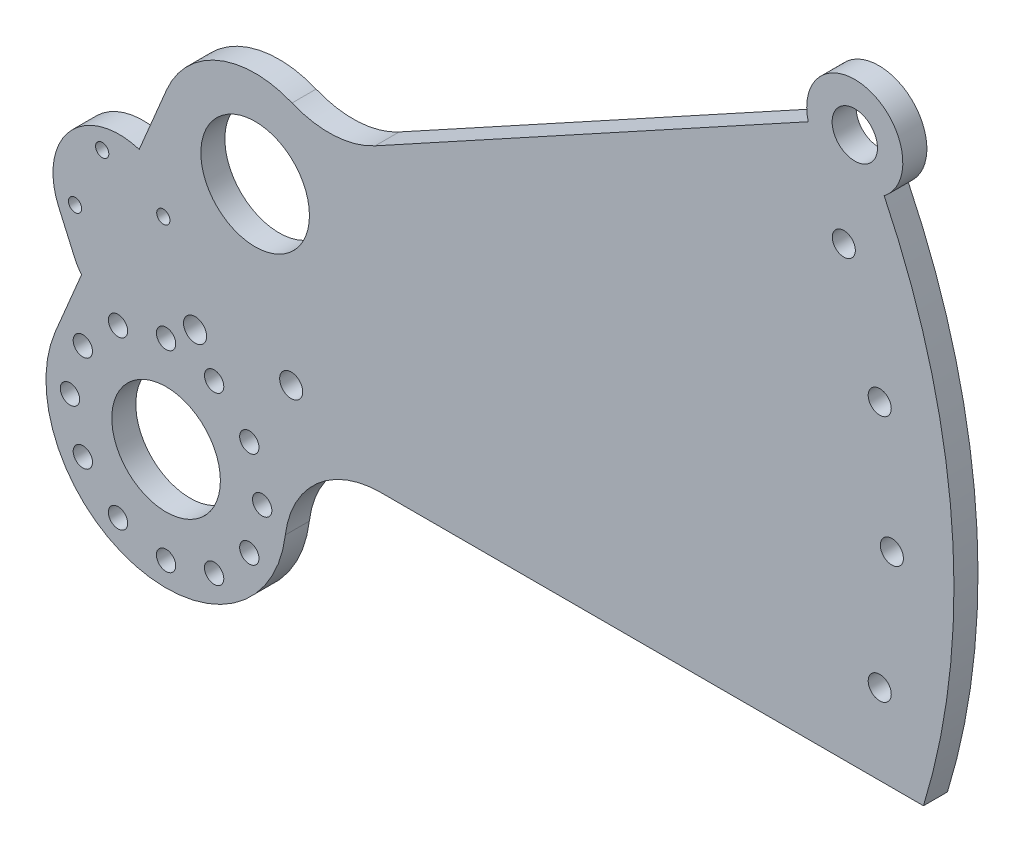
SolidWorks part; units mm, degrees
material "6061-T6 (SS)"
ref_plane "Front Plane" through (0, 0, 0) normal (0, 0, 1) x (1, 0, 0)
ref_plane "Top Plane" through (0, 0, 0) normal (0, 1, 0) x (1, 0, 0)
ref_plane "Right Plane" through (0, 0, 0) normal (1, 0, 0) x (0, 0, -1)
ref_plane "Plane1" through (0, 0, 0) normal (0, 0, -1) x (-1, 0, 0)
sketch "Sketch1" plane through (0, 0, 0) normal (0, 0, -1) x (-1, 0, 0)
  line L7 (-31.7217, 24.6299) -> (-146.1701, 87.3654)
  line L8 (-176.627, -53.975) -> (-33.1944, -53.975)
  line L9 (52.8124, -60.1841) -> (45.8592, -43.6206)
  line L10 (47.5699, -41.0132) -> (51.9346, -31.1397)
  line L11 (30.6457, -7.3807) -> (23.42, 9.8317)
  line L12 (0, 0) -> (35.9287, -24.0642) construction
  line L13 (35.9287, -24.0642) -> (47.5935, -28.5567) construction
  line L14 (35.9287, -24.0642) -> (40.4212, -12.3994) construction
  line L15 (35.9287, -24.0642) -> (24.2639, -19.5717) construction
  line L16 (35.9287, -24.0642) -> (46.3362, -24.0642) construction
  line L17 (23.5374, -72.4737) -> (0, 0) construction
  line L18 (48.9374, -72.4737) -> (23.5374, -72.4737) construction
  line L19 (23.5374, -72.4737) -> (48.9374, -72.4737) construction
  line L20 (15.875, -41.275) -> (0, 0) construction
  line L21 (-9.525, -41.275) -> (15.875, -41.275) construction
  line L22 (-207.782, -132.6531) -> (-57.7705, -132.6531) construction
  line L23 (-57.7705, -132.6531) -> (92.241, -132.6531) construction
  line L24 (0, 0) -> (-168.275, 0) construction
  line L25 (-165.0688, -32.6918) -> (0, 0) construction
  line L26 (0, 0) -> (-165.0688, 32.6918) construction
  line L27 (-155.5725, 64.1379) -> (0, 0) construction
  line L28 (-165.0688, -32.6918) -> (-168.275, 0) construction
  line L29 (-168.275, 0) -> (-165.0688, 32.6918) construction
  line L30 (-165.0688, 32.6918) -> (-155.5725, 64.1379) construction
  circle A0 centre (40.4212, -12.3994) radius 1.75
  circle A1 centre (47.5935, -28.5567) radius 1.75
  circle A2 centre (15.875, -41.275) radius 3.048
  circle A3 centre (45.5344, -85.1737) radius 2.5527
  circle A4 centre (48.9374, -72.4737) radius 2.5527
  circle A5 centre (23.5374, -72.4737) radius 14.351
  circle A6 centre (-9.525, -41.275) radius 3.048
  circle A11 centre (-165.0688, 32.6918) radius 3.048
  circle A12 centre (-165.0688, -32.6918) radius 3.048
  circle A22 centre (-155.5725, 64.1379) radius 3.048
  circle A23 centre (-168.275, 0) radius 3.048
  circle A24 centre (0, 0) radius 14.351
  circle A38 centre (24.2639, -19.5717) radius 1.75
  circle A39 centre (-158.4749, 90.5087) radius 5.9944
  arc A40 (-146.1701, 87.3654) -> (-166.2421, 80.4608) centre (-158.4749, 90.5087) ccw
  arc A41 (-166.2421, 80.4608) -> (-176.627, -53.975) centre (0, 0) ccw
  arc A42 (-33.1944, -53.975) -> (-7.9803, -76.3077) centre (-33.1944, -79.375) cw
  arc A43 (-7.9803, -76.3077) -> (52.8124, -60.1841) centre (23.5374, -72.4737) ccw
  arc A44 (45.8592, -43.6206) -> (47.5699, -41.0132) centre (38.8582, -37.1622) ccw
  arc A45 (51.9346, -31.1397) -> (30.6457, -7.3807) centre (35.9287, -24.0642) ccw
  arc A46 (23.42, 9.8317) -> (-9.7563, 23.4515) centre (0, 0) ccw
  arc A47 (-9.7563, 23.4515) -> (-31.7217, 24.6299) centre (-19.5126, 46.9031) cw
  circle A48 centre (36.2374, -94.4707) radius 2.5527
  circle A49 centre (23.5374, -97.8737) radius 2.5527
  circle A50 centre (10.8374, -94.4707) radius 2.5527
  circle A51 centre (1.5403, -85.1737) radius 2.5527
  circle A52 centre (-1.8626, -72.4737) radius 2.5527
  circle A53 centre (1.5403, -59.7737) radius 2.5527
  circle A54 centre (10.8374, -50.4766) radius 2.5527
  circle A55 centre (23.5374, -47.0737) radius 2.5527
  circle A56 centre (36.2374, -50.4766) radius 2.5527
  circle A57 centre (45.5344, -59.7737) radius 2.5527
  arc A58 (-165.0688, -32.6918) -> (-155.5725, 64.1379) centre (0, 0) cw construction
  dimension "D1" = 28.702
  dimension "D6" = 3.5
  dimension "D7" = 76.2
  dimension "D10" = 5.1054
  dimension "D14" = 6.096
  dimension "D19" = 31.75
  dimension "D20" = 25.4
  dimension "D22" = 9.525
  dimension "D24" = 17.5
  dimension "D26" = 168.275
  dimension "D2" = 35.9287
  dimension "D3" = 24.0642
  dimension "D4" = 12.5
  dimension "D5" = 21.063
  dimension "D8" = 23.5374
  dimension "D9" = 25.4
  dimension "D12" = 25.4
  dimension "D13" = 12.7
  dimension "D15" = 44.2226
  dimension "D16" = 41.275
  dimension "D17" = 25.4
  dimension "D18" = 12.7
  dimension "D21" = 17.9637
  dimension "D23" = 9.8736
  dimension "D25" = 16.5634
  dimension "D27" = 11.202
  dimension "D11" = 12
extrude "Boss-Extrude1" add sketch "Sketch1" against normal blind 6.35
